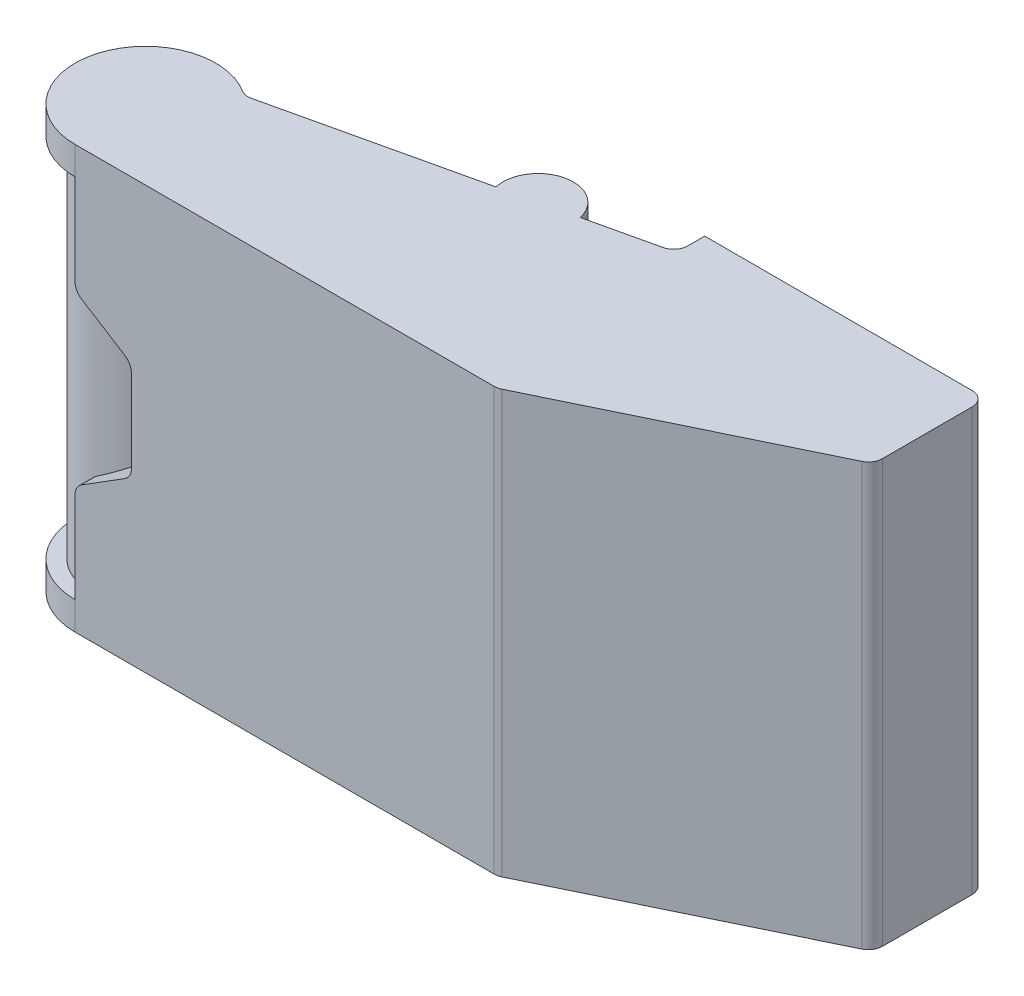
SolidWorks part; units mm, degrees
ref_plane "前视基准面" through (0, 0, 0) normal (0, 0, 1) x (1, 0, 0)
ref_plane "上视基准面" through (0, 0, 0) normal (0, 1, 0) x (1, 0, 0)
ref_plane "右视基准面" through (0, 0, 0) normal (1, 0, 0) x (0, 0, -1)
sketch "草图1" plane through (0, 0, 0) normal (0, 1, 0) x (1, 0, 0)
  line L0 (0, -5) -> (29.7706, -5)
  line L1 (30.2065, -4.9) -> (48, 3.7178)
  line L2 (48, 3.7178) -> (48, 11.7178)
  line L3 (48, 11.7178) -> (28, 11.7178)
  line L4 (28, 11.7178) -> (28, 10.5149)
  line L5 (27.223, 9.5401) -> (3.4275, 4.0978)
  line L6 (-3.95, 0) -> (3.95, 0)
  line L7 (0, -5) -> (29.7706, -5)
  line L8 (0, -5) -> (0, -3.95)
  line L9 (2.5695, -3) -> (30, -3)
  line L10 (30, -4.9733) -> (30, -3)
  arc A0 (2.6704, 4.2272) -> (0, -5) centre (0, 0) ccw
  arc A1 (2.5695, -3) -> (0, -3.95) centre (0, 0) ccw
  arc A2 (29.7706, -5) -> (30.2065, -4.9) centre (29.7706, -4) ccw
  arc A3 (28, 10.5149) -> (27.223, 9.5401) centre (27, 10.5149) cw
  arc A4 (3.4275, 4.0978) -> (2.6704, 4.2272) centre (3.2045, 5.0726) cw
  arc A5 (0, -3.95) -> (2.5695, -3) centre (0, 0) ccw
  point P20 (28, 9.7178)
  point P23 (3, 4)
  dimension "D1" = 10
  dimension "D9" = 7.9
  dimension "D11" = 1
  dimension "D2" = 9
  dimension "D6" = 20
  dimension "D7" = 8
  dimension "D8" = 2
extrude "凸台-拉伸1" add sketch "草图1" along normal blind 2 contours L5 A4 A0 L8 A1 L9 L10 A2 L1 L2 L3 L4 A3 region at (26.0339, 0, -3.5603)
extrude "凸台-拉伸2" add sketch "草图1<3>" along normal blind 30 contours L0 A2 L10 L9 L8 region at (15.4011, 0, 4.0176)
sketch "草图1<3>" plane through (0, 0, 0) normal (0, 1, 0) x (1, 0, 0) same geometry as "草图1"
sketch "草图2" plane through (0, 30, 0) normal (0, 1, 0) x (1, 0, 0)
  line L4 (0, -5) -> (29.7706, -5)
  line L5 (30, -4.9733) -> (30, -3)
  line L6 (30, -3) -> (2.5695, -3)
  line L7 (0, -3.95) -> (0, -5)
  line L10 (30, -3) -> (2.5695, -3)
  line L11 (0, -3.95) -> (0, -5)
  line L16 (27.223, 9.5401) -> (3.4275, 4.0978)
  line L17 (0, -5) -> (0, -3.95)
  line L18 (2.5695, -3) -> (30, -3)
  line L19 (30, -3) -> (30, -4.9733)
  line L20 (30.2065, -4.9) -> (48, 3.7178)
  line L21 (48, 3.7178) -> (48, 11.7178)
  line L22 (48, 11.7178) -> (28, 11.7178)
  line L23 (28, 11.7178) -> (28, 10.5149)
  line L24 (27.223, 9.5401) -> (3.4275, 4.0978)
  line L25 (0, -5) -> (0, -3.95)
  line L26 (2.5695, -3) -> (30, -3)
  line L27 (30, -3) -> (30, -4.9733)
  line L28 (30.2065, -4.9) -> (48, 3.7178)
  line L29 (48, 3.7178) -> (48, 11.7178)
  line L30 (48, 11.7178) -> (28, 11.7178)
  line L31 (28, 11.7178) -> (28, 10.5149)
  arc A1 (29.7706, -5) -> (30, -4.9733) centre (29.7706, -4) ccw
  arc A2 (29.7706, -5) -> (30, -4.9733) centre (29.7706, -4) ccw
  arc A4 (0, -3.95) -> (2.5695, -3) centre (0, 0) ccw
  arc A5 (0, -3.95) -> (2.5695, -3) centre (0, 0) ccw
  arc A7 (2.6704, 4.2272) -> (3.4275, 4.0978) centre (3.2045, 5.0726) ccw
  arc A8 (2.6704, 4.2272) -> (0, -5) centre (0, 0) ccw
  arc A9 (2.5695, -3) -> (0, -3.95) centre (0, 0) ccw
  arc A10 (30, -4.9733) -> (30.2065, -4.9) centre (29.7706, -4) ccw
  arc A11 (27.223, 9.5401) -> (28, 10.5149) centre (27, 10.5149) ccw
  arc A12 (2.6704, 4.2272) -> (3.4275, 4.0978) centre (3.2045, 5.0726) ccw
  arc A13 (2.6704, 4.2272) -> (0, -5) centre (0, 0) ccw
  arc A14 (2.5695, -3) -> (0, -3.95) centre (0, 0) ccw
  arc A15 (30, -4.9733) -> (30.2065, -4.9) centre (29.7706, -4) ccw
  arc A16 (27.223, 9.5401) -> (28, 10.5149) centre (27, 10.5149) ccw
  line M21 (30, -4.9733) -> (30, -3)
  line M22 (30, -3) -> (2.5695, -3)
  dimension "D1" = 0
  dimension "D2" = 0
extrude "凸台-拉伸3" add sketch "草图2" against normal blind 2 contours A16 L24 A12 A13 L11 A14 A15 L28 L29 L30 L31 M22 M21 region at (26.0339, 30, -3.5603)
extrude "凸台-拉伸5" add sketch "草图1<5>" along normal up to surface (30 mm away) contours A1 A5 | L6 A1 region at (0, 0, 1.6764) region at (0, 0, -1.6764) up to face at (23.9323, 30, -4.2174)
sketch "草图1<5>" plane through (0, 0, 0) normal (0, 1, 0) x (1, 0, 0) same geometry as "草图1"
sketch "草图4" plane through (0, 0, 5) normal (0, 0, 1) x (1, 0, 0)
  line L0 (0, 15) -> (50000, 15) construction
  line L1 (0, 28) -> (0, 2) construction
  line L2 (0, 21) -> (4, 18.5)
  line L3 (4, 18.5) -> (4, 11.5)
  line L4 (4, 11.5) -> (0, 9)
  line L5 (0, 9) -> (0, 21)
  point P4 (0, 15)
  dimension "D1" = 7
  dimension "D2" = 12
  dimension "D3" = 4
extrude "切除-拉伸2" cut sketch "草图4" against normal up to next
sketch "草图5" plane through (0, 30, 0) normal (0, 1, 0) x (1, 0, 0)
  circle A0 centre (0, 0) radius 3.95
  dimension "D1" = 7.9
extrude "凸台-拉伸6" add sketch "草图5" against normal through all
fillet "圆角1" radius 1 4 edges at (4, 11.5, 4) (4, 18.5, 4) (0, 21, 4.475) (0, 9, 4.475)
sketch "草图6" plane through (0, 2, 0) normal (0, 1, 0) x (1, 0, 0)
  line L0 (28, 11.7178) -> (28, 10.7178)
  line L1 (28, 11.7178) -> (28, 10.5149) construction
  line L2 (28, 10.7178) -> (47, 10.7178)
  line L3 (47, 10.7178) -> (47, 4.3446)
  line L4 (48, 3.7178) -> (48, 11.7178) construction
  line L6 (28, 11.7178) -> (48, 11.7178)
  line L7 (48, 11.7178) -> (28, 11.7178) construction
  line L8 (48, 11.7178) -> (48, 3.7178)
  line L10 (47, 4.3446) -> (29.7706, -4)
  line L11 (29.7706, -4) -> (29.7706, -5)
  line L12 (30.2065, -4.9) -> (48, 3.7178) construction
  line L13 (30.2065, -4.9) -> (48, 3.7178)
  arc A0 (29.7706, -5) -> (30.2065, -4.9) centre (29.7706, -4) ccw construction
  arc A1 (29.7706, -5) -> (30.2065, -4.9) centre (29.7706, -4) ccw
  dimension "D1" = 1
  dimension "D2" = 1
  dimension "D3" = 1
extrude "凸台-拉伸7" add sketch "草图6" along normal up to surface (26 mm away) up to face at (20.728, 28, -3.0345)
fillet "圆角2" radius 1 2 edges at (48, 15, -11.7178) (48, 15, -3.7178)
sketch "草图7" plane through (0, 30, 0) normal (0, 1, 0) x (1, 0, 0)
  line L0 (27.223, 9.5401) -> (3.4275, 4.0978) construction
  line L1 (22.4366, 8.4454) -> (17.5625, 7.3306)
  circle A0 centre (19.9995, 7.888) radius 2.5
  line M7 (27.223, 9.5401) -> (3.4275, 4.0978)
  dimension "D2" = 2.5
  dimension "D1" = 17
extrude "凸台-拉伸8" add sketch "草图7" against normal up to surface (30 mm away) contours A0 M7 | A0 M7 region at (20.2361, 30, -6.8537) region at (19.763, 30, -8.9223) up to face at (27.8413, 0, -4.7574)
sketch "草图8" plane through (0, 2, 0) normal (0, 1, 0) x (1, 0, 0)
  line L9 (27.223, 9.5401) -> (22.4366, 8.4454)
  line L10 (17.5625, 7.3306) -> (3.4275, 4.0978)
  line L11 (0, -5) -> (0, -3.95)
  line L12 (2.5695, -3) -> (30, -3)
  line L13 (30, -3) -> (30, -3.8889)
  line L14 (30, -3.8889) -> (47, 4.3446)
  line L15 (47, 4.3446) -> (47, 10.7178)
  line L16 (47, 10.7178) -> (28, 10.7178)
  line L17 (28, 10.7178) -> (28, 10.5149)
  circle A0 centre (19.9995, 7.888) radius 2.5
  circle A1 centre (19.9995, 7.888) radius 2
  arc A5 (17.5625, 7.3306) -> (22.4366, 8.4454) centre (19.9995, 7.888) ccw
  arc A6 (2.6704, 4.2272) -> (3.4275, 4.0978) centre (3.2045, 5.0726) ccw
  arc A7 (2.6704, 4.2272) -> (0, -5) centre (0, 0) ccw
  arc A8 (2.5695, -3) -> (0, -3.95) centre (0, 0) ccw
  arc A9 (27.223, 9.5401) -> (28, 10.5149) centre (27, 10.5149) ccw
  arc A10 (17.5625, 7.3306) -> (22.4366, 8.4454) centre (19.9995, 7.888) ccw construction
  arc M16 (22.4366, 8.4454) -> (17.5625, 7.3306) centre (19.9995, 7.888) cw
  dimension "D2" = 4
  dimension "D1" = 0
extrude "切除-拉伸3" cut sketch "草图8" along normal blind 3 from offset 12 contours A0 A1 M16 region at (22.4135, 2, -8.1605)
